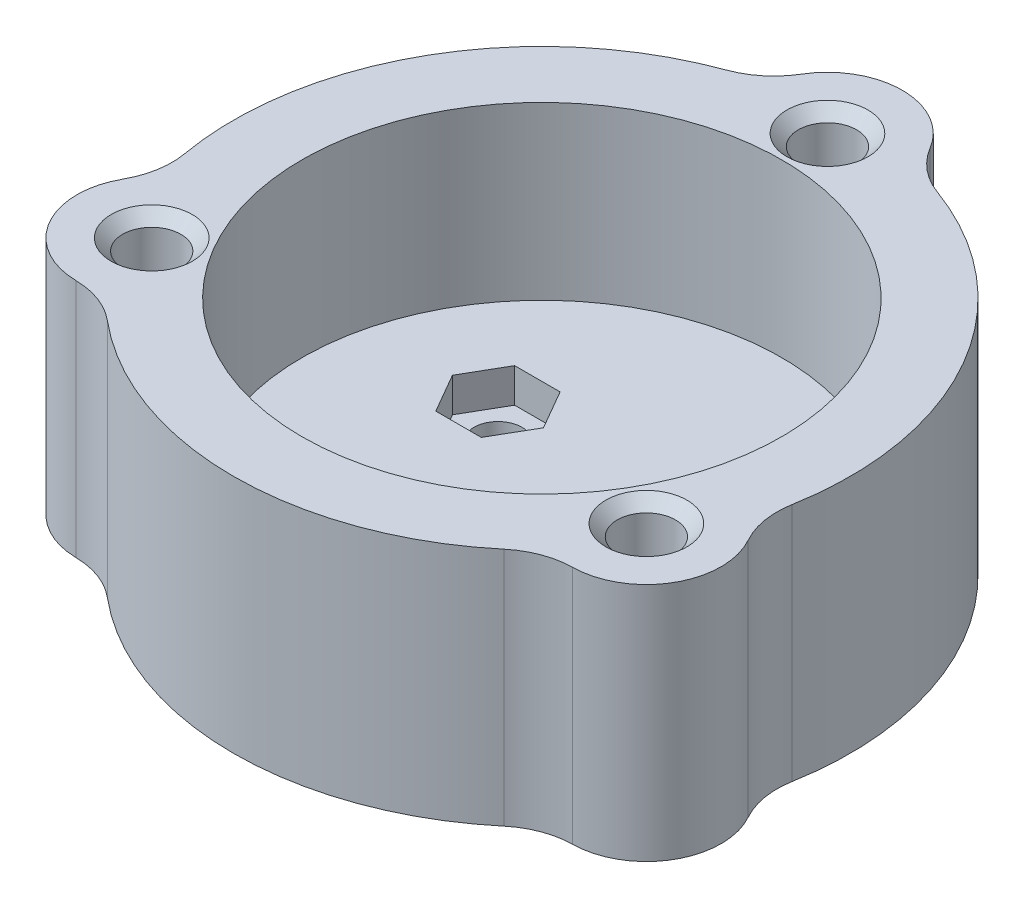
SolidWorks part; units mm, degrees
ref_plane "Спереди" through (0, 0, 0) normal (0, 0, 1) x (1, 0, 0)
ref_plane "Сверху" through (0, 0, 0) normal (0, 1, 0) x (1, 0, 0)
ref_plane "Справа" through (0, 0, 0) normal (1, 0, 0) x (0, 0, -1)
sketch "Эскиз1" plane through (0, 0, 0) normal (0, 1, 0) x (1, 0, 0)
  circle A0 centre (0, 0) radius 25 construction
  circle A1 centre (0, 25) radius 2.55
  circle A3 centre (0, 25) radius 6.55
  circle A4 centre (0, 0) radius 21
  circle A5 centre (0, 0) radius 27
  circle A6 centre (21.6506, -12.5) radius 6.55
  circle A7 centre (21.6506, -12.5) radius 2.55
  circle A8 centre (-21.6506, -12.5) radius 6.55
  circle A9 centre (-21.6506, -12.5) radius 2.55
  dimension "D1" = 50
  dimension "D2" = 5.1
  dimension "D3" = 4
  dimension "D5" = 4
  dimension "D4" = 2
  dimension "D6" = 3
extrude "Бобышка-Вытянуть1" add sketch "Эскиз1" along normal blind 15 contours A5 A3 A1 | A3 A5 A1 A4 | A6 A5 A3 A4 | A8 A4 A3 A5 | A7 A5 A6 A4 | A7 A5 A6 | A8 A5 A6 A4 | A9 A5 A8 | A9 A5 A8 A4 region at (2.4448, 0, -26.1369) region at (0, 0, -28.7811) region at (18.7721, 0, -10.8381) region at (-18.7721, 0, -10.8381) region at (-23.1355, 0, 6.2905) region at (-24.9251, 0, 14.3905) region at (24.9251, 0, 14.3905) region at (24.991, 0, 9.7744) region at (0, 0, 21.6761)
sketch "Эскиз2" plane through (0, 0, 0) normal (0, -1, 0) x (1, 0, 0)
  arc A27 (25.9264, 7.5381) -> (19.4914, 18.6839) centre (21.6506, 12.5) ccw
  arc A28 (6.435, -26.2219) -> (25.9264, 7.5381) centre (0, 0) ccw
  arc A29 (-6.435, -26.2219) -> (6.435, -26.2219) centre (0, -25) ccw
  arc A30 (-25.9264, 7.5381) -> (-6.435, -26.2219) centre (0, 0) ccw
  arc A31 (-19.4914, 18.6839) -> (-25.9264, 7.5381) centre (-21.6506, 12.5) ccw
  arc A32 (19.4914, 18.6839) -> (-19.4914, 18.6839) centre (0, 0) ccw
  arc A33 (25.9264, 7.5381) -> (19.4914, 18.6839) centre (21.6506, 12.5) ccw
  arc A34 (6.435, -26.2219) -> (25.9264, 7.5381) centre (0, 0) ccw
  arc A35 (-6.435, -26.2219) -> (6.435, -26.2219) centre (0, -25) ccw
  arc A36 (-25.9264, 7.5381) -> (-6.435, -26.2219) centre (0, 0) ccw
  arc A37 (-19.4914, 18.6839) -> (-25.9264, 7.5381) centre (-21.6506, 12.5) ccw
  arc A38 (19.4914, 18.6839) -> (-19.4914, 18.6839) centre (0, 0) ccw
  dimension "D1" = 0
extrude "Бобышка-Вытянуть2" add sketch "Эскиз2" along normal blind 6
fillet "Скругление1" radius 7 6 edges at (6.435, 4.5, -26.2219) (-6.435, 4.5, -26.2219) (-25.9264, 4.5, 7.5381) (-19.4914, 4.5, 18.6839) (19.4914, 4.5, 18.6839) (25.9264, 4.5, 7.5381)
chamfer "Фаска1" distance 1 angle 45 3 edges at (0, 15, -22.45) (21.6506, 15, 15.05) (-21.6506, 15, 15.05)
sketch "Эскиз3" plane through (0, -6, 0) normal (0, -1, 0) x (1, 0, 0)
  circle A0 centre (0, 0) radius 10.5 construction
  circle A1 centre (0, 10.5) radius 2.1
  circle A2 centre (9.0933, -5.25) radius 2.1
  circle A3 centre (-9.0933, -5.25) radius 2.1
  dimension "D1" = 21
  dimension "D2" = 4.2
  dimension "D3" = 3
extrude "Вырез-Вытянуть1" cut sketch "Эскиз3" against normal through all
sketch "Эскиз4" plane through (0, 0, 0) normal (0, 1, 0) x (1, 0, 0)
  line L0 (-3.9837, -10.5) -> (-1.9919, -13.95)
  line L1 (11.0851, 1.8) -> (13.077, 5.25)
  line L2 (13.077, 5.25) -> (11.0851, 8.7)
  line L3 (11.0851, 8.7) -> (7.1014, 8.7)
  line L4 (7.1014, 8.7) -> (5.1095, 5.25)
  line L5 (5.1095, 5.25) -> (7.1014, 1.8)
  line L6 (7.1014, 1.8) -> (11.0851, 1.8)
  line L7 (-1.9919, -13.95) -> (1.9919, -13.95)
  line L8 (1.9919, -13.95) -> (3.9837, -10.5)
  line L9 (3.9837, -10.5) -> (1.9919, -7.05)
  line L10 (1.9919, -7.05) -> (-1.9919, -7.05)
  line L11 (-1.9919, -7.05) -> (-3.9837, -10.5)
  line L12 (-7.1014, 8.7) -> (-11.0851, 8.7)
  line L13 (-11.0851, 8.7) -> (-13.077, 5.25)
  line L14 (-13.077, 5.25) -> (-11.0851, 1.8)
  line L15 (-11.0851, 1.8) -> (-7.1014, 1.8)
  line L16 (-7.1014, 1.8) -> (-5.1095, 5.25)
  line L17 (-5.1095, 5.25) -> (-7.1014, 8.7)
  circle A0 centre (9.0933, 5.25) radius 3.45 construction
  circle A1 centre (0, -10.5) radius 3.45 construction
  circle A2 centre (-9.0933, 5.25) radius 3.45 construction
  circle A3 centre (0, -10.5) radius 2.1 construction
  dimension "D1" = 6.9
  dimension "D2" = 3
extrude "Вырез-Вытянуть2" cut sketch "Эскиз4" against normal blind 3
equation "\"motor_diameter\"= 30"
equation "\"mm_diameter\"= IIF ( \"motor_diameter\" < 34 , 41 , \"motor_diameter\" + 8 )"
equation "\"upper_shafts_diameter\"= 5"
equation "\"upper_shats_length\"= 180"
equation "\"upper_bearing_d1\"= 10"
equation "\"upper_bearing_d2\"= 5"
equation "\"upper_bearing_h\"= 15"
equation "\"lower_shafts_diameter\"= 5"
equation "\"lower_shafts_length\"= 180"
equation "\"lower_bearing_d1\"= 10"
equation "\"lower_bearing_d2\"= 5"
equation "\"lower_bearing_h\"= 15"
equation "\"print_offset\"= 0.2"
equation "\"bh_screws_d\"= 2"
equation "\"bh_screws_h\"= 20"
equation "\"bh_screws_hh_d\"= 3.4"
equation "\"bh_screws_hh_h\"= 2"
equation "\"bh_nut_d\"= 3.8"
equation "\"bh_nut_h\"= 2"
equation "\"motor_screws_d\"= 3"
equation "\"motor_screws_h\"= 16"
equation "\"motor_screws_hh_d\"= 5.5"
equation "\"motor_screws_hh_h\"= 3"
equation "\"plate_hole_distance\"= 25.4"
equation "\"plate_screws_d\"= 6.5"
equation "\"shafts_diameter\"= IIF ( \"mm_diameter\" < 42 , 42 + 8 , \"mm_diameter\" + 8 )"
equation "\"central_hole_diameter\"= 8"
equation "\"bh_thikness\"= 4"
equation "\"D1@Эскиз1\"=\"shafts_diameter\""
equation "\"D2@Эскиз1\" = \"lower_shafts_diameter\" + \"print_offset\" / 2"
equation "\"D3@Эскиз1\"=\"bh_thikness\""
equation "\"D5@Эскиз1\"=\"D3@Эскиз1\""
equation "\"D1@Бобышка-Вытянуть1\"= \"lower_bearing_h\""
equation "\"D1@Бобышка-Вытянуть2\"=6"
equation "\"D4@Эскиз1\"=\"D3@Эскиз1\"/2"
equation "\"ends_screws_d\"= 4"
equation "\"ends_screws_h\"= 16"
equation "\"ends_screws_hh_d\"= 6.7"
equation "\"ends_screws_hh_h\"= 4.1"
equation "\"ends_nut_d\"= 6.8"
equation "\"ends_nut_h\"= 3"
equation "\"D2@Эскиз3\"=\"ends_screws_d\"+\"print_offset\""
equation "\"D1@Эскиз4\"=\"ends_nut_d\"+\"print_offset\"/2"
equation "\"D1@Вырез-Вытянуть2\"=\"ends_nut_h\""
